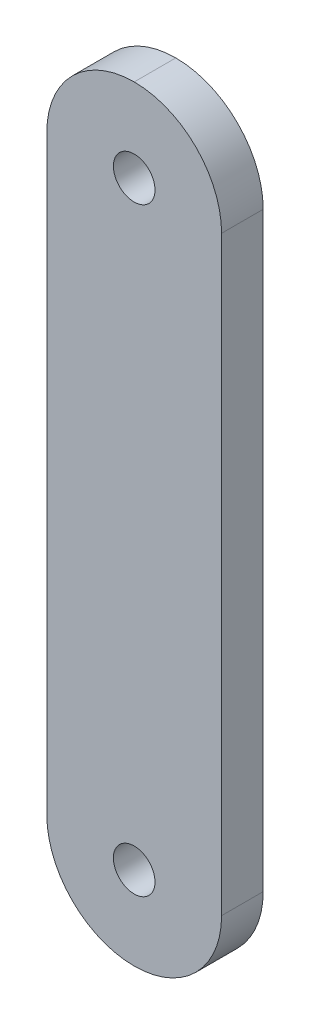
SolidWorks part; units mm, degrees
ref_plane "前视基准面" through (0, 0, 0) normal (0, 0, 1) x (1, 0, 0)
ref_plane "上视基准面" through (0, 0, 0) normal (0, 1, 0) x (1, 0, 0)
ref_plane "右视基准面" through (0, 0, 0) normal (1, 0, 0) x (0, 0, -1)
sketch "草图1" plane through (0, 0, 0) normal (0, 0, 1) x (1, 0, 0)
  line L1 (-59.6571, 37.1143) -> (-38.6571, 37.1143)
  line L2 (-59.6571, 37.1143) -> (-59.6571, -54.8857)
  line L3 (-59.6571, -54.8857) -> (-38.6571, -54.8857)
  line L4 (-38.6571, 37.1143) -> (-38.6571, -54.8857)
  dimension "D1" = 92
  dimension "D2" = 21
extrude "凸台-拉伸1" add sketch "草图1" along normal blind 5
sketch "草图3" plane through (0, 0, 5) normal (0, 0, 1) x (1, 0, 0)
  line L0 (-59.6571, -54.8857) -> (-38.6571, -54.8857) construction
  line L1 (-38.6571, -54.8857) -> (-38.6571, 37.1143) construction
  circle A0 centre (-49.1571, -44.8857) radius 2.5
  dimension "D1" = 10
  dimension "D2" = 10.5
extrude "切除-拉伸1" cut sketch "草图3" against normal blind 15
sketch "草图4" plane through (0, 0, 5) normal (0, 0, 1) x (1, 0, 0)
  line L0 (-38.6571, 37.1143) -> (-59.6571, 37.1143) construction
  line L1 (-38.6571, -54.8857) -> (-38.6571, 37.1143) construction
  circle A0 centre (-49.1571, 27.1143) radius 2.5
  dimension "D1" = 10
  dimension "D2" = 10.5
extrude "切除-拉伸2" cut sketch "草图4" against normal blind 15
fillet "圆角2" radius 10.5 4 edges at (-38.6571, 37.1143, 2.5) (-59.6571, 37.1143, 2.5) (-38.6571, -54.8857, 2.5) (-59.6571, -54.8857, 2.5)
sketch "草图5" plane through (0, 0, 5) normal (0, 0, 1) x (1, 0, 0)
  point P0 (-49.1571, -44.8857)
